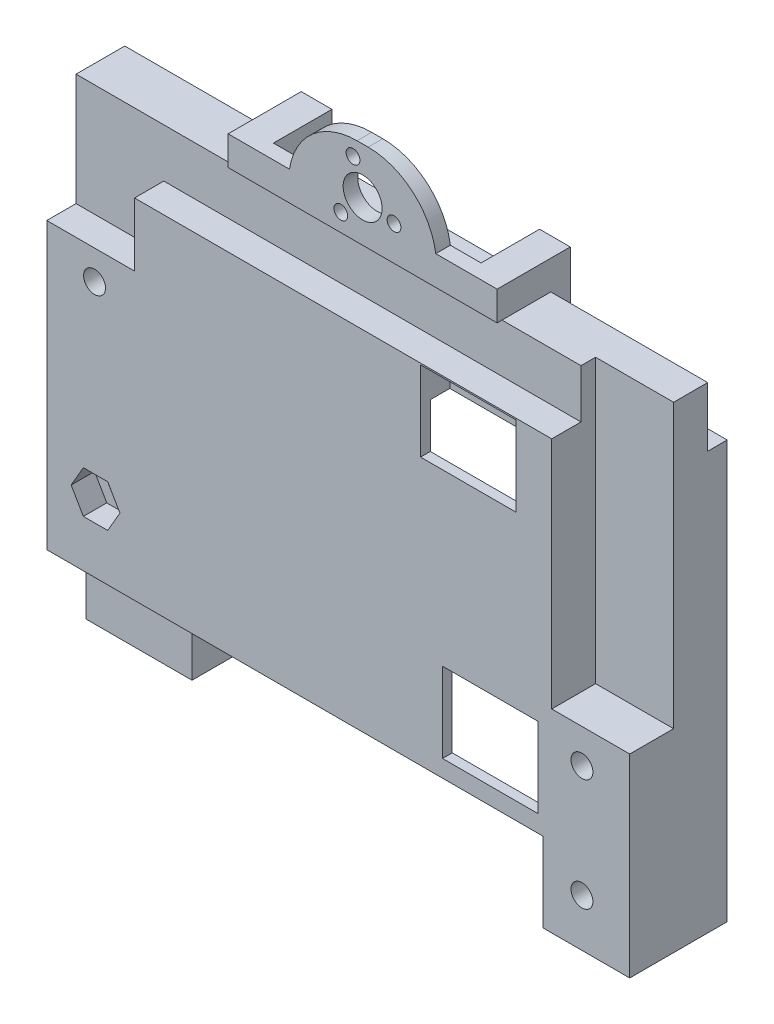
SolidWorks part; units mm, degrees
ref_plane "Front Plane" through (0, 0, 0) normal (0, 0, 1) x (1, 0, 0)
ref_plane "Top Plane" through (0, 0, 0) normal (0, 1, 0) x (1, 0, 0)
ref_plane "Right Plane" through (0, 0, 0) normal (1, 0, 0) x (0, 0, -1)
sketch "Sketch1" plane through (0, 0, 0) normal (0, 0, 1) x (1, 0, 0)
  line L0 (-10.8323, 19.4357) -> (-26.9323, 19.4357)
  line L1 (-26.9323, 41.8597) -> (-26.9323, -23.3643) construction
  line L2 (-26.9323, 19.4357) -> (-26.9323, -23.3643)
  line L3 (-26.9323, -23.3643) -> (32.8677, -23.3643)
  line L4 (32.8677, -23.3643) -> (32.8677, 19.4357)
  line L5 (32.8677, -23.3643) -> (32.8677, 41.8597) construction
  line L6 (32.8677, 19.4357) -> (16.7677, 19.4357)
  line L7 (16.7677, 19.4357) -> (16.7677, 36.0357)
  line L8 (16.7677, 36.0357) -> (-10.8323, 36.0357)
  line L9 (-10.8323, 36.0357) -> (-10.8323, 19.4357)
  line L11 (-15.5323, -1.4643) -> (-24.2323, -1.4643)
  line L12 (-24.2323, -1.4643) -> (-24.2323, 19.4357)
  line L13 (-15.5323, -1.4643) -> (-15.5323, 19.4357)
  line L14 (30.1677, -1.4643) -> (30.1677, 19.4357)
  line L15 (30.1677, -1.4643) -> (21.4677, -1.4643)
  line L16 (21.4677, -1.4643) -> (21.4677, 19.4357)
  circle A0 centre (2.9677, 29.7857) radius 6
  dimension "D1" = 12
extrude "Boss-Extrude1" add sketch "Sketch1" along normal up to surface (6 mm away) contours L15 L16 L6 L7 L8 L9 L0 L13 L11 L12 L2 L3 L4 L14 A0 region at (2.9677, 0.4107, 0)
sketch "Sketch2" plane through (0, 0, 6) normal (0, 0, 1) x (1, 0, 0)
  line L0 (-10.8323, 36.0357) -> (-10.8323, 19.4357)
  line L1 (-10.8323, 19.4357) -> (16.7677, 19.4357)
  line L2 (16.7677, 19.4357) -> (16.7677, 36.0357)
  line L3 (16.7677, 36.0357) -> (-10.8323, 36.0357)
  circle A0 centre (2.9677, 29.7857) radius 2
  circle A1 centre (1.9825, 32.9352) radius 0.705
  circle A2 centre (6.1879, 29.0643) radius 0.705
  circle A3 centre (0.7329, 27.3577) radius 0.705
  circle M1 centre (2.9677, 29.7857) radius 6
  line M6 (16.7677, 19.4357) -> (16.7677, 36.0357)
  line M7 (16.7677, 36.0357) -> (-10.8323, 36.0357)
  line M8 (-10.8323, 36.0357) -> (-10.8323, 19.4357)
  dimension "D1" = 4
  dimension "D2" = 1.41
  dimension "D3" = 1.41
  dimension "D4" = 1.41
extrude "Boss-Extrude2" add sketch "Sketch2" along normal blind 1.5 contours L1 M8 M6 M7 M1 | A3 A2 A1 A0 M1 region at (2.9677, 36.0035, 6) region at (-2.8625, 29.7857, 6)
sketch "Sketch3" plane through (0, 0, 6) normal (0, 0, 1) x (1, 0, 0)
  line L0 (-26.9323, 19.4357) -> (-26.9323, 25.5357)
  line L1 (-26.9323, 41.8597) -> (-26.9323, -23.3643) construction
  line L2 (-26.9323, 25.5357) -> (32.8677, 25.5357)
  line L3 (32.8677, -23.3643) -> (32.8677, 41.8597) construction
  line L4 (32.8677, 25.5357) -> (32.8677, 19.4357)
  line L5 (32.8677, 19.4357) -> (32.8677, -1.4643)
  line L6 (32.8677, -23.3643) -> (32.8677, 19.4357) construction
  line L7 (32.8677, -1.4643) -> (-26.9323, -1.4643)
  line L8 (-26.9323, 19.4357) -> (-26.9323, -23.3643) construction
  line L9 (-26.9323, -1.4643) -> (-26.9323, 19.4357)
  circle A0 centre (2.9675, 29.7857) radius 6
  line M3 (16.7677, 19.4357) -> (-10.8323, 19.4357)
  line M4 (-10.8323, 19.4357) -> (-15.5323, 19.4357)
  line M5 (-15.5323, 19.4357) -> (-15.5323, -1.4643)
  line M6 (-15.5323, -1.4643) -> (-24.2323, -1.4643)
  line M7 (-24.2323, -1.4643) -> (-24.2323, 19.4357)
  line M8 (-24.2323, 19.4357) -> (-26.9323, 19.4357)
  line M12 (32.8677, 19.4357) -> (30.1677, 19.4357)
  line M13 (30.1677, 19.4357) -> (30.1677, -1.4643)
  line M14 (30.1677, -1.4643) -> (21.4677, -1.4643)
  line M15 (21.4677, -1.4643) -> (21.4677, 19.4357)
  line M16 (21.4677, 19.4357) -> (16.7677, 19.4357)
  dimension "D2" = 12
  dimension "D1" = 27
extrude "Boss-Extrude3" add sketch "Sketch3" against normal blind 4 contours A0 L2 L0 L4 M8 M7 M6 M5 M4 M3 M16 M15 M14 M13 M12 region at (-26.2761, 22.4857, 6)
sketch "Sketch5" plane through (0, 0, 0) normal (0, 0, -1) x (-1, 0, 0)
  line L0 (-23.9677, 16.7857) -> (-23.9677, -21.9643)
  line L1 (-23.9677, -21.9643) -> (16.0323, -21.9643)
  line L2 (16.0323, -21.9643) -> (16.0323, 16.7857)
  line L3 (16.0323, 16.7857) -> (-23.9677, 16.7857)
  line L4 (26.9323, -23.3643) -> (-32.8677, -23.3643) construction
  line L5 (-22.9677, -13.2143) -> (-22.9677, 16.7857) construction
  line L6 (17.0323, 16.7857) -> (17.0323, -13.2143) construction
  line L7 (-22.9677, 16.7857) -> (17.0323, 16.7857) construction
  dimension "D1" = 1.4
  dimension "D2" = 1
  dimension "D3" = 1
  dimension "D4" = 0
extrude "Cut-Extrude1" cut sketch "Sketch5" against normal through all
sketch "Sketch6" plane through (0, 0, 6) normal (0, 0, 1) x (1, 0, 0)
  line L0 (-26.9323, 25.5357) -> (32.8677, 25.5357)
  line L1 (32.8677, 25.5357) -> (32.8677, -15.2143)
  line L2 (32.8677, -23.3643) -> (32.8677, 25.5357) construction
  line L3 (32.8677, -15.2143) -> (-26.9323, -15.2143)
  line L4 (-26.9323, 25.5357) -> (-26.9323, -23.3643) construction
  line L5 (-26.9323, -15.2143) -> (-26.9323, 25.5357)
  line L6 (-17.0323, -13.2143) -> (22.9677, -13.2143) construction
  dimension "D1" = 2
extrude "Boss-Extrude4" add sketch "Sketch6" along normal up to surface (4 mm away)
sketch "Sketch7" plane through (0, 0, 6) normal (0, 0, -1) x (-1, 0, 0)
  line L0 (-23.9677, 16.7857) -> (16.0323, 16.7857)
  line L1 (16.0323, 16.7857) -> (16.0323, -21.9643)
  line L2 (16.0323, -21.9643) -> (-23.9677, -21.9643)
  line L3 (-23.9677, -21.9643) -> (-23.9677, 16.7857)
extrude "Cut-Extrude2" cut sketch "Sketch7" against normal blind 3
sketch "Sketch8" plane through (0, 0, 10) normal (0, 0, 1) x (1, 0, 0)
  line L0 (19.1177, 19.3857) -> (13.5177, 19.3857) construction
  line L1 (13.661, -13.4643) -> (23.4745, -13.4643)
  line L2 (13.661, -13.4643) -> (13.661, -5.2643)
  line L3 (13.661, -5.2643) -> (23.4745, -5.2643)
  line L4 (23.4745, -13.4643) -> (23.4745, -5.2643)
  line L5 (13.661, -13.4643) -> (23.4745, -5.2643) construction
  line L6 (13.661, -5.2643) -> (23.4745, -13.4643) construction
  line L7 (11.411, 12.1857) -> (21.2245, 12.1857)
  line L8 (11.411, 12.1857) -> (11.411, 20.3857)
  line L9 (11.411, 20.3857) -> (21.2245, 20.3857)
  line L10 (21.2245, 12.1857) -> (21.2245, 20.3857)
  line L11 (11.411, 12.1857) -> (21.2245, 20.3857) construction
  line L12 (11.411, 20.3857) -> (21.2245, 12.1857) construction
  line L13 (12.411, 18.8857) -> (12.411, 18.1857) construction
  line L14 (21.3677, -6.2643) -> (15.7677, -6.2643) construction
  line L15 (14.661, -6.7643) -> (14.661, -7.4643) construction
  line L16 (32.8677, -3.4643) -> (24.8677, -3.4643)
  line L17 (32.8677, -15.2143) -> (32.8677, 25.5357) construction
  line L18 (24.8677, -3.4643) -> (24.8677, 20.5357)
  line L19 (24.8677, 20.5357) -> (-17.9323, 20.5357)
  line L20 (-17.9323, 20.5357) -> (-17.9323, 14.0357)
  line L21 (-17.9323, 14.0357) -> (-26.9323, 14.0357)
  line L22 (-26.9323, 25.5357) -> (-26.9323, -15.2143) construction
  line L23 (-26.9323, 14.0357) -> (-26.9323, 25.5357)
  line L24 (-26.9323, 25.5357) -> (32.8677, 25.5357)
  line L25 (32.8677, 25.5357) -> (32.8677, -3.4643)
  line L26 (-26.9323, -15.2143) -> (-16.4323, -15.2143)
  line L27 (-26.9323, -15.2143) -> (-26.9323, -23.3643) construction
  line L28 (-16.4323, -15.2143) -> (-16.4323, -23.3643)
  line L29 (-26.9323, -23.3643) -> (32.8677, -23.3643) construction
  line L30 (-16.4323, -23.3643) -> (-26.9323, -23.3643)
  line L31 (-26.9323, -23.3643) -> (-26.9323, -15.2143)
  line L32 (-26.9323, -15.2143) -> (32.8677, -15.2143) construction
  point P0 (18.5677, -9.3643)
  point P6 (16.3177, 16.2857)
  line M17 (32.8677, 25.5357) -> (-26.9323, 25.5357)
  line M18 (-26.9323, 25.5357) -> (-26.9323, -15.2143)
  line M19 (-26.9323, -15.2143) -> (32.8677, -15.2143)
  line M20 (32.8677, -15.2143) -> (32.8677, 25.5357)
  dimension "D1" = 1
  dimension "D2" = 1
  dimension "D3" = 1
  dimension "D4" = 1
  dimension "D5" = 10.5
  dimension "D6" = 0
  dimension "D7" = 29
  dimension "D8" = 8
  dimension "D9" = 5
  dimension "D10" = 9
  dimension "D11" = 11.5
extrude "Cut-Extrude3" cut sketch "Sketch8" against normal blind 3 contours L21 L20 L19 L18 L16 M20 M17 M18 | L31 L30 L28 M19 region at (28.8677, -2.7996, 10) region at (-21.6823, -19.2893, 10)
extrude "Cut-Extrude4" cut sketch "Sketch8<3>" against normal up to surface (1 mm away) contours L7 L10 L9 L8 | L1 L4 L3 L2 region at (18.5677, -9.3643, 10) region at (16.3177, 16.2857, 10) up to face at (3.9677, 0.7857, 9)
sketch "Sketch8<3>" plane through (0, 0, 10) normal (0, 0, 1) x (1, 0, 0) same geometry as "Sketch8"
sketch "Sketch9" plane through (0, 0, 7.5) normal (0, 0, 1) x (1, 0, 0)
  line L0 (24.8677, 20.5357) -> (24.8677, -3.4643)
  line L1 (24.8677, -3.4643) -> (32.8677, -3.4643)
  line L2 (32.8677, -3.4643) -> (32.8677, 25.5357)
  line L6 (24.8677, 20.5357) -> (24.8677, 25.5357)
  line L7 (32.8677, 25.5357) -> (16.7677, 25.5357) construction
  line L8 (24.8677, 25.5357) -> (32.8677, 25.5357)
extrude "Cut-Extrude5" cut sketch "Sketch9" against normal blind 2
sketch "Sketch10" plane through (0, 0, 6) normal (0, 0, 1) x (1, 0, 0)
  line L0 (23.9677, -15.2143) -> (32.8677, -15.2143)
  line L1 (32.8677, -15.2143) -> (32.8677, -23.3643)
  line L2 (32.8677, -23.3643) -> (23.9677, -23.3643)
  line L3 (-26.9323, -23.3643) -> (32.8677, -23.3643) construction
  line L4 (23.9677, -23.3643) -> (23.9677, -15.2143)
extrude "Boss-Extrude5" add sketch "Sketch10" along normal up to surface (4 mm away) up to face at (16.3177, 16.2857, 10)
sketch "Sketch11" plane through (0, 0, 2) normal (0, 0, -1) x (-1, 0, 0)
  line L0 (-21.4677, 19.4357) -> (-21.4677, -1.4643)
  line L1 (-21.4677, -1.4643) -> (-30.1677, -1.4643)
  line L2 (-30.1677, -1.4643) -> (-30.1677, 19.4357)
  line L3 (-30.1677, 19.4357) -> (-21.4677, 19.4357)
  line L4 (15.5323, 19.4357) -> (24.2323, 19.4357)
  line L5 (24.2323, 19.4357) -> (24.2323, -1.4643)
  line L6 (24.2323, -1.4643) -> (15.5323, -1.4643)
  line L7 (15.5323, -1.4643) -> (15.5323, 19.4357)
sketch "Sketch12" plane through (0, 0, 7.5) normal (0, 0, 1) x (1, 0, 0)
  line L0 (2.9675, 29.7857) -> (2.9675, 36.0357)
  line L1 (16.7677, 36.0357) -> (-10.8323, 36.0357) construction
  line L2 (2.9675, 36.0357) -> (10.4675, 36.0357)
  line L3 (10.4675, 36.0357) -> (10.4675, 34.5357)
  line L4 (10.4675, 34.5357) -> (-4.5325, 34.5357)
  line L5 (-4.5325, 34.5357) -> (-4.5325, 36.0357)
  line L6 (-4.5325, 36.0357) -> (2.9675, 36.0357)
  line M8 (16.7677, 36.0357) -> (-10.8323, 36.0357)
  dimension "D1" = 15
  dimension "D2" = 1.5
  dimension "D3" = 7.5
extrude "Cut-Extrude7" cut sketch "Sketch12" against normal through all contours L5 L4 L0 M8 | L4 L3 L0 M8 region at (-0.7825, 35.2857, 7.5) region at (6.7175, 35.2857, 7.5)
sketch "Sketch13" plane through (0, 0, 10) normal (0, 0, 1) x (1, 0, 0)
  line L0 (-26.9323, -15.2143) -> (23.9677, -15.2143) construction
  line L1 (-19.4323, -8.2143) -> (-20.6823, -6.0492)
  line L2 (-20.6823, -6.0492) -> (-23.1823, -6.0492)
  line L3 (-23.1823, -6.0492) -> (-24.4323, -8.2143)
  line L4 (-24.4323, -8.2143) -> (-23.1823, -10.3793)
  line L5 (-23.1823, -10.3793) -> (-20.6823, -10.3793)
  line L6 (-20.6823, -10.3793) -> (-19.4323, -8.2143)
  line L7 (-26.9323, 14.0357) -> (-26.9323, -15.2143) construction
  circle A0 centre (-21.9323, -8.2143) radius 2.1651 construction
  dimension "D1" = 2.5
  dimension "D2" = 7
  dimension "D3" = 5
extrude "Cut-Extrude8" cut sketch "Sketch13" against normal blind 2.4
sketch "Sketch15" plane through (-203.3718, 125.6825, 5.6002) normal (0, 0, 1) x (1, 0, 0)
  line L0 (185.4396, -111.6468) -> (176.4396, -111.6468) construction
  line L1 (183.8396, -114.6468) -> (182.5896, -112.4817)
  line L2 (182.5896, -112.4817) -> (180.0896, -112.4817)
  line L3 (180.0896, -112.4817) -> (178.8396, -114.6468)
  line L4 (178.8396, -114.6468) -> (180.0896, -116.8119)
  line L5 (180.0896, -116.8119) -> (182.5896, -116.8119)
  line L6 (182.5896, -116.8119) -> (183.8396, -114.6468)
  line L7 (180.0896, -112.4817) -> (176.4396, -112.4817)
  line L8 (176.4396, -111.6468) -> (176.4396, -140.8968) construction
  line L9 (176.4396, -112.4817) -> (176.4396, -116.8119)
  line L10 (176.4396, -116.8119) -> (180.0896, -116.8119)
  circle A0 centre (181.3396, -114.6468) radius 2.1651 construction
  dimension "D1" = 2.5
extrude "Cut-Extrude9" cut sketch "Sketch15" against normal blind 2.4 contours L5 L6 L1 L2 L3 L4 | L9 L10 L4 L3 L7 region at (-22.0323, 11.0357, 5.6002) region at (-25.3982, 11.0357, 5.6002)
sketch "Sketch16" plane through (0, 0, 10) normal (0, 0, 1) x (1, 0, 0)
  circle A0 centre (-21.9323, -8.2143) radius 1.125
  circle A1 centre (-22.0323, 11.0357) radius 1.125
  circle A2 centre (27.9677, -6.9643) radius 1.125
  circle A3 centre (27.9677, -18.4643) radius 1.125
  dimension "D1" = 2.25
  dimension "D2" = 2.25
  dimension "D3" = 2.25
  dimension "D4" = 2.25
extrude "Cut-Extrude10" cut sketch "Sketch16" against normal through all
sketch "Sketch17" plane through (0, 0, 0) normal (0, 0, -1) x (-1, 0, 0)
  line L0 (-22.9677, 16.7857) -> (-23.9677, 16.7857)
  line L1 (-23.9677, 16.7857) -> (-23.9677, -14.2143)
  line L3 (18.0323, -14.2143) -> (18.0323, 16.7857)
  line L4 (18.0323, 16.7857) -> (-23.9677, 16.7857)
  line L5 (-22.9677, 16.7857) -> (-22.9677, -13.2143) construction
  line L6 (17.0323, -13.2143) -> (17.0323, 16.7857) construction
  line L8 (-23.9677, -14.2143) -> (18.0323, -14.2143)
  line L9 (-22.9677, -13.2143) -> (17.0323, -13.2143) construction
  dimension "D1" = 1
  dimension "D2" = 1
  dimension "D3" = 1
extrude "Cut-Extrude11" cut sketch "Sketch17" against normal blind 8.5 contours L1 L8 L3 L4
sketch "Sketch19" plane through (0, 0, 6) normal (0, 0, -1) x (-1, 0, 0)
  line L0 (-13.6176, 36.0357) -> (-13.6176, 23.7857)
  line L1 (-16.7677, 36.0357) -> (-10.4675, 36.0357) construction
  line L2 (-13.6176, 23.7857) -> (7.6824, 23.7857)
  line L3 (7.6824, 23.7857) -> (7.6824, 36.0357)
  line L4 (4.5325, 36.0357) -> (10.8323, 36.0357) construction
  line L5 (7.6824, 36.0357) -> (-13.6176, 36.0357)
  dimension "D1" = 12.25
extrude "Cut-Extrude12" cut sketch "Sketch19" along normal through all
sketch "Sketch20" plane through (0, 0, 7.5) normal (0, 0, 1) x (1, 0, 0)
  line L8 (13.6176, 36.0357) -> (13.6176, 23.7857) construction
  line L11 (-7.6824, 28.5357) -> (-4.5325, 28.5357)
  line L14 (13.6176, 28.5357) -> (10.4675, 28.5357)
  line L15 (-7.6824, 28.5357) -> (-7.6824, 36.0357)
  line L16 (-7.6824, 36.0357) -> (-4.5325, 36.0357)
  line L18 (10.4675, 28.5357) -> (10.4675, 36.0357)
  line L19 (10.4675, 36.0357) -> (13.6176, 36.0357)
  line L20 (16.7677, 36.0357) -> (10.4675, 36.0357) construction
  line L21 (13.6176, 36.0357) -> (13.6176, 28.5357)
  line L22 (-4.5325, 36.0357) -> (-4.5325, 28.5357)
  dimension "D1" = 3.1499
  dimension "D2" = 3.1501
  dimension "D3" = 7.5
  dimension "D4" = 7.5
extrude "Cut-Extrude13" cut sketch "Sketch20" against normal through all
fillet "Fillet1" radius 7 2 edges at (-4.5325, 34.5357, 6.75) (10.4675, 34.5357, 6.75)
sketch "Sketch21" plane through (0, 0, 6) normal (0, 0, 1) x (1, 0, 0)
  line L0 (-16.0323, -21.9643) -> (-16.0323, -23.3643)
  line L1 (-26.9323, -23.3643) -> (23.9677, -23.3643) construction
  line L2 (-16.0323, -23.3643) -> (-11.0323, -23.3643)
  line L3 (-11.0323, -23.3643) -> (-11.0323, -21.9643)
  line L4 (31.4677, -21.9643) -> (-25.5323, -21.9643) construction
  line L5 (-11.0323, -21.9643) -> (-16.0323, -21.9643)
  dimension "D1" = 5
extrude "Cut-Extrude14" cut sketch "Sketch21" against normal through all
sketch "Sketch22" plane through (0, 0, 9) normal (0, 0, 1) x (1, 0, 0)
  line L0 (11.411, 16.7857) -> (11.411, 20.3857)
  line L1 (11.411, 20.3857) -> (21.2245, 20.3857)
  line L2 (21.2245, 20.3857) -> (21.2245, 16.7857)
  line L3 (21.2245, 16.7857) -> (11.411, 16.7857)
extrude "Cut-Extrude15" cut sketch "Sketch22" against normal blind 2
sketch "Sketch23" plane through (0, 0, 7.5) normal (0, 0, 1) x (1, 0, 0)
  line L0 (-7.6824, 28.5357) -> (-7.6824, 36.0357)
  line L1 (-7.6824, 36.0357) -> (-10.8323, 36.0357)
  line L2 (-10.8323, 36.0357) -> (-10.8323, 28.5357)
  line L3 (-10.8323, 36.0357) -> (-10.8323, 25.5357) construction
  line L4 (-10.8323, 28.5357) -> (-7.6824, 28.5357)
  line L5 (13.6176, 28.5357) -> (13.6176, 36.0357)
  line L6 (13.6176, 36.0357) -> (16.7677, 36.0357)
  line L7 (16.7677, 36.0357) -> (16.7677, 28.5357)
  line L8 (16.7677, 25.5357) -> (16.7677, 36.0357) construction
  line L9 (16.7677, 28.5357) -> (13.6176, 28.5357)
extrude "Cut-Extrude16" cut sketch "Sketch23" against normal through all
sketch "Sketch24" plane through (0, 0, 0) normal (0, 0, -1) x (-1, 0, 0)
  line L0 (-23.9677, -21.9643) -> (-23.9677, -23.3643)
  line L1 (-23.9677, -23.3643) -> (11.0323, -23.3643)
  line L2 (11.0323, -23.3643) -> (11.0323, -21.9643)
  line L3 (11.0323, -21.9643) -> (-23.9677, -21.9643)
extrude "Cut-Extrude17" cut sketch "Sketch24" against normal through all
equation "\"M2_screw_head_hole\"= 4.5"
equation "\"M2_screw_shaft_hole\"=2.25"
equation "\"D1@Sketch16\"=\"M2_screw_shaft_hole\""
equation "\"D2@Sketch16\"=\"M2_screw_shaft_hole\""
equation "\"D3@Sketch16\"=\"M2_screw_shaft_hole\""
equation "\"D4@Sketch16\"=\"M2_screw_shaft_hole\""
